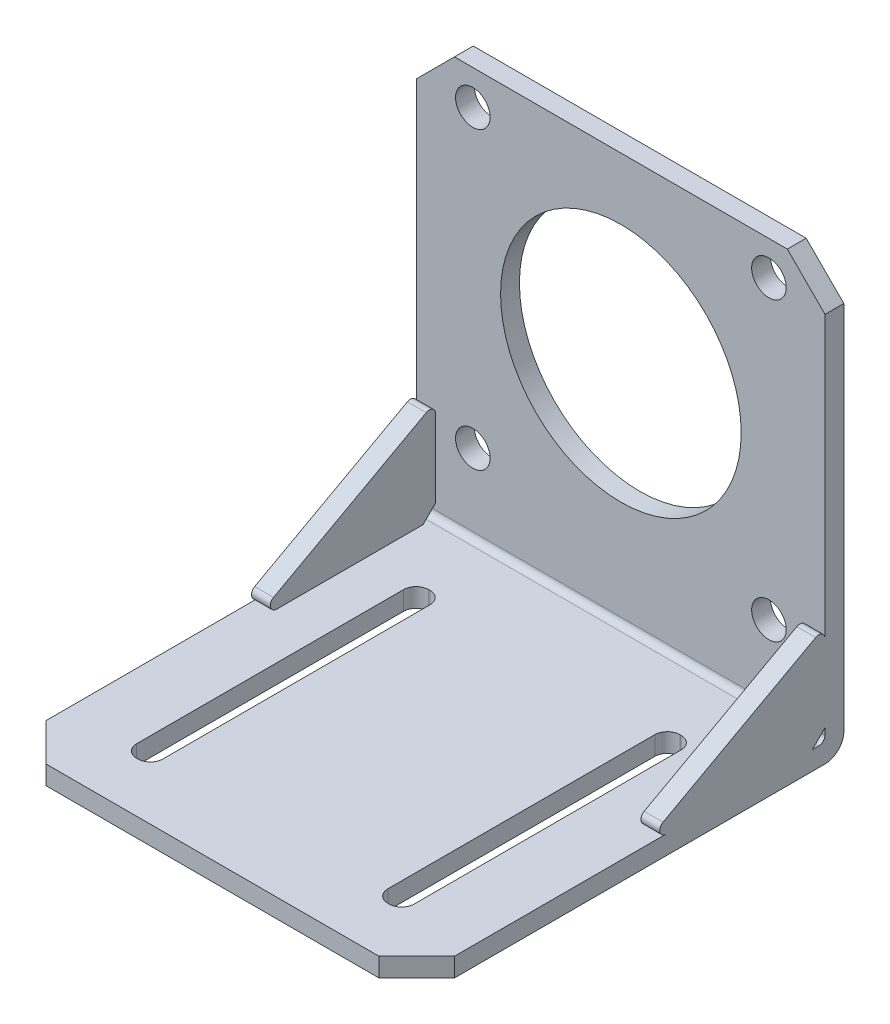
SolidWorks part; units mm, degrees
ref_plane "Спереди" through (0, 0, 0) normal (0, 0, 1) x (1, 0, 0)
ref_plane "Сверху" through (0, 0, 0) normal (0, 1, 0) x (1, 0, 0)
ref_plane "Справа" through (0, 0, 0) normal (1, 0, 0) x (0, 0, -1)
sketch "Эскиз1" plane through (0, 0, 0) normal (0, 1, 0) x (1, 0, 0)
  line L1 (-32.5, -34) -> (32.5, -34)
  line L2 (-32.5, -34) -> (-32.5, 34)
  line L3 (-32.5, 34) -> (32.5, 34)
  line L4 (32.5, -34) -> (32.5, 34)
  line L5 (-32.5, -34) -> (32.5, 34) construction
  line L6 (-32.5, 34) -> (32.5, -34) construction
  line L8 (0, -42.3568) -> (0, 41.0664) construction
  line L9 (-19.9, 20.5) -> (-20.1, 20.5)
  line L10 (-17.9, 18.5) -> (-17.9, -24)
  line L11 (-19.9, -26) -> (-20.1, -26)
  line L12 (-22.1, 18.5) -> (-22.1, -24)
  line L13 (-17.9, 20.5) -> (-22.1, -26) construction
  line L14 (-17.9, -26) -> (-22.1, 20.5) construction
  line L15 (17.9, -26) -> (22.1, 20.5) construction
  line L16 (17.9, 20.5) -> (22.1, -26) construction
  line L17 (22.1, 18.5) -> (22.1, -24)
  line L18 (19.9, -26) -> (20.1, -26)
  line L19 (17.9, 18.5) -> (17.9, -24)
  line L20 (19.9, 20.5) -> (20.1, 20.5)
  line L22 (-32.5, 34) -> (32.5, 34)
  line L23 (-32.5, 34) -> (-32.5, 31)
  line L24 (-32.5, 31) -> (32.5, 31)
  line L25 (32.5, 34) -> (32.5, 31)
  arc A0 (-20.1, -26) -> (-22.1, -24) centre (-20.1, -24) cw
  arc A1 (-17.9, -24) -> (-19.9, -26) centre (-19.9, -24) cw
  arc A2 (-19.9, 20.5) -> (-17.9, 18.5) centre (-19.9, 18.5) cw
  arc A3 (-20.1, 20.5) -> (-22.1, 18.5) centre (-20.1, 18.5) ccw
  arc A4 (20.1, 20.5) -> (22.1, 18.5) centre (20.1, 18.5) cw
  arc A5 (19.9, 20.5) -> (17.9, 18.5) centre (19.9, 18.5) ccw
  arc A6 (17.9, -24) -> (19.9, -26) centre (19.9, -24) ccw
  arc A7 (20.1, -26) -> (22.1, -24) centre (20.1, -24) ccw
  point P0 (0, 0)
  point P10 (-20, -2.75)
  point P45 (20, -2.75)
  dimension "D9" = 2
  dimension "D1" = 65
  dimension "D2" = 68
  dimension "D3" = 8
  dimension "D4" = 12.5
  dimension "D7" = 46.5
  dimension "D8" = 4.2
  dimension "D10" = 3
extrude "Бобышка-Вытянуть1" add sketch "Эскиз1" along normal blind 3 contours L24 L2 L1 L4 A7 L18 A6 L19 A5 L20 A4 L17 A3 L9 A2 L10 A1 L11 A0 L12 region at (0, 0, 1.3751)
extrude "Бобышка-Вытянуть2" add sketch "Эскиз1<3>" along normal blind 68 contours L2 L24 L4 L3 region at (0, 0, -32.5)
sketch "Эскиз1<3>" plane through (0, 0, 0) normal (0, 1, 0) x (1, 0, 0) same geometry as "Эскиз1"
chamfer "Фаска1" distance 6 distance2 6 4 edges at (32.5, 68, -32.5) (-32.5, 68, -32.5) (32.5, 1.5, 34) (-32.5, 1.5, 34)
sketch "Эскиз3" plane through (0, 0, -34) normal (0, 0, -1) x (-1, 0, 0)
  line L3 (26.5, 68) -> (-26.5, 68) construction
  line L4 (-40.4386, 39) -> (40.5359, 39) construction
  circle A0 centre (0, 39) radius 19.15
  circle A1 centre (-23.57, 62.57) radius 2.75
  circle A2 centre (23.57, 62.5) radius 2.75
  circle A3 centre (23.57, 15.5) radius 2.75
  circle A4 centre (-23.57, 15.43) radius 2.75
  dimension "D1" = 38.3
  dimension "D2" = 29
  dimension "D3" = 23.57
  dimension "D6" = 5.5
  dimension "D4" = 23.57
  dimension "D5" = 23.57
extrude "Вырез-Вытянуть1" cut sketch "Эскиз3" against normal up to next
fillet "Скругление1" radius 3 1 edges at (0, 0, -34)
fillet "Скругление2" radius 1 1 edges
sketch "Эскиз5" plane through (-32.5, 0, 0) normal (-1, 0, 0) x (0, 0, 1)
  line L0 (-31, 5) -> (-31, 17.3124)
  line L1 (-31, 62) -> (-31, 4) construction
  line L2 (-29.5197, 18.1895) -> (-5.2066, 4.8771)
  line L3 (28, 3) -> (-30, 3) construction
  line L4 (-5.6869, 3) -> (-29, 3)
  line L5 (-29, 3) -> (-31, 5)
  arc A0 (-5.2066, 4.8771) -> (-5.6869, 3) centre (-5.6869, 4) cw
  arc A1 (-31, 17.3124) -> (-29.5197, 18.1895) centre (-30, 17.3124) cw
  point P0 (-31, 3)
  point P9 (-1.7783, 3)
  point P12 (-31, 19)
  dimension "D1" = 1
  dimension "D2" = 2
  dimension "D3" = 45
extrude "Бобышка-Вытянуть3" add sketch "Эскиз5" against normal blind 3
extrude "Бобышка-Вытянуть4" add sketch "Эскиз5<2>" along normal blind 3 from vertex starting at point (32.5, 4, -31)
sketch "Эскиз5<2>" plane through (-32.5, 0, 0) normal (-1, 0, 0) x (0, 0, 1) same geometry as "Эскиз5"
